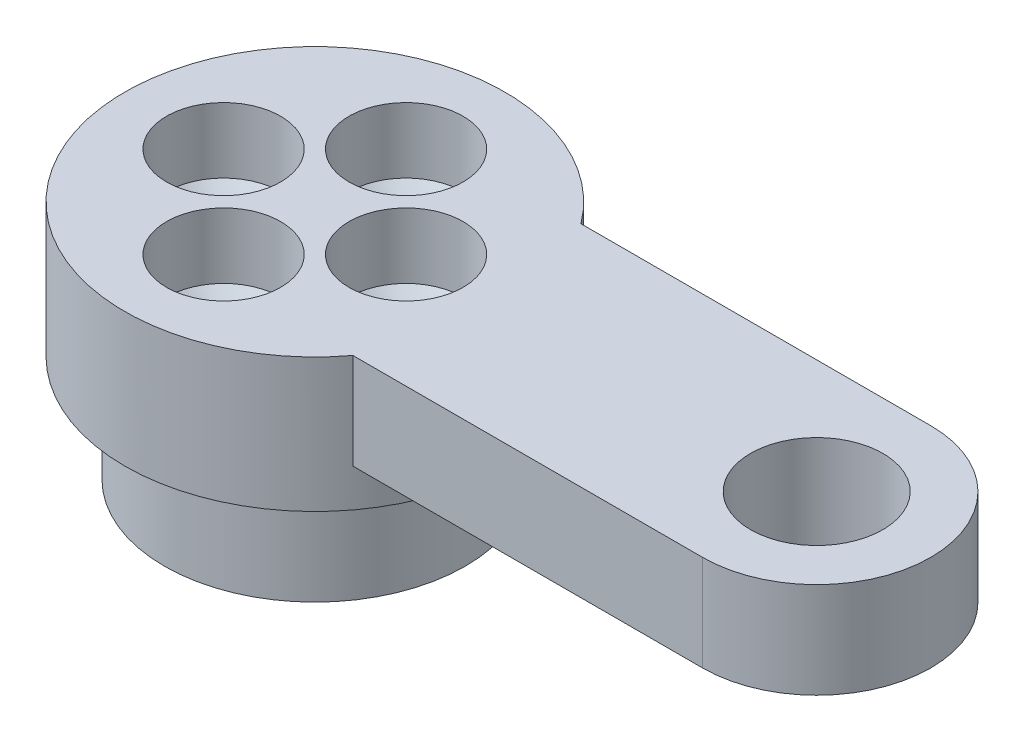
SolidWorks part; units mm, degrees
material "ABS"
ref_plane "前视基准面" through (0, 0, 0) normal (0, 0, 1) x (1, 0, 0)
ref_plane "上视基准面" through (0, 0, 0) normal (0, 1, 0) x (1, 0, 0)
ref_plane "右视基准面" through (0, 0, 0) normal (1, 0, 0) x (0, 0, -1)
sketch "草图1" plane through (0, 0, 0) normal (0, 1, 0) x (1, 0, 0)
  line L0 (-1000, 0) -> (49000, 0) construction
  circle A0 centre (0, 0) radius 9.9
  circle A1 centre (6, 0) radius 1.85
  circle A2 centre (0, -6) radius 1.85
  circle A3 centre (-6, 0) radius 1.85
  circle A4 centre (0, 6) radius 1.85
  point P16 (0, 0)
  dimension "D1" = 19.8
  dimension "D2" = 3.7
  dimension "D3" = 6
  dimension "D4" = 4
extrude "凸台-拉伸1" add sketch "草图1" along normal blind 7
sketch "草图2" plane through (0, 7, 0) normal (0, 1, 0) x (1, 0, 0)
  circle A0 centre (0, 0) radius 12.5
  circle A1 centre (-6, 0) radius 1.85 construction
  circle A2 centre (0, -6) radius 1.85 construction
  circle A3 centre (6, 0) radius 1.85 construction
  circle A4 centre (0, 6) radius 1.85 construction
  circle A5 centre (-6, 0) radius 1.85
  circle A6 centre (0, -6) radius 1.85
  circle A7 centre (6, 0) radius 1.85
  circle A8 centre (0, 6) radius 1.85
  dimension "D1" = 25
extrude "凸台-拉伸2" add sketch "草图2" along normal blind 2.5
sketch "草图3" plane through (0, 9.5, 0) normal (0, 1, 0) x (1, 0, 0)
  line L0 (-1000, 0) -> (49000, 0) construction
  line L1 (33, -7.5) -> (10, -7.5)
  line L2 (33, 7.5) -> (10, 7.5)
  circle A0 centre (0, -6) radius 1.85 construction
  circle A1 centre (-6, 0) radius 1.85 construction
  circle A2 centre (0, 6) radius 1.85 construction
  circle A3 centre (6, 0) radius 1.85 construction
  circle A4 centre (0, 0) radius 12.5 construction
  circle A5 centre (0, -6) radius 1.85
  circle A6 centre (-6, 0) radius 1.85
  circle A7 centre (0, 6) radius 1.85
  circle A8 centre (6, 0) radius 1.85
  circle A9 centre (0, 0) radius 12.5
  circle A10 centre (33, 0) radius 4.35
  circle A11 centre (6, 0) radius 3.75
  circle A12 centre (0, -6) radius 3.75
  circle A13 centre (-6, 0) radius 3.75
  circle A14 centre (0, 6) radius 3.75
  circle A15 centre (33, 0) radius 7.5
  point P29 (0, 0)
  circle M13 centre (0, 0) radius 12.5
  dimension "D1" = 8.7
  dimension "D2" = 7.5
  dimension "D4" = 33
  dimension "D5" = 15
  dimension "D3" = 4
extrude "凸台-拉伸3" add sketch "草图3" along normal blind 6.3 contours L0 A9 A11 A13 A12 M13 | L0 A13 A11 A9 A14 M13 | A9 L0 A15 L2 | L0 L1 A15 M13 | L0 A15 A10 | A15 L0 A10 region at (-6, 9.5, -4.0295) region at (0, 9.5, 0.2795) region at (19.4799, 9.5, -4.0658) region at (19.4799, 9.5, 4.0658) region at (27.8153, 9.5, -5.1847) region at (27.075, 9.5, 0.1677)
chamfer "倒角1" distance 2 angle 45 4 edges at (0, 9.5, 9.75) (-6, 9.5, 3.75) (0, 9.5, -2.25) (6, 9.5, 3.75)
